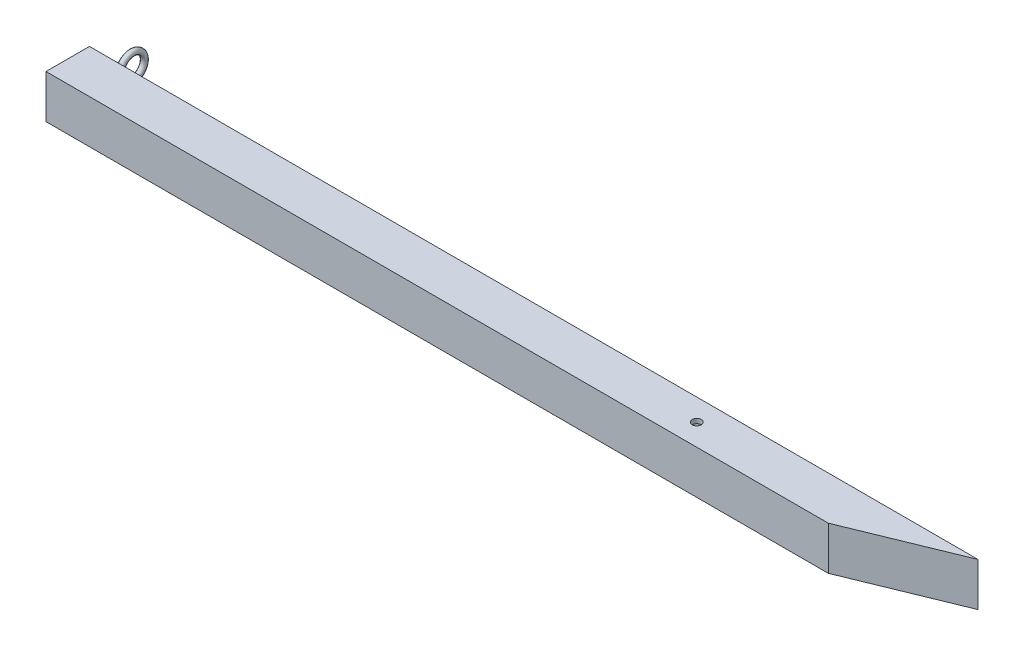
SolidWorks part; units mm, degrees
ref_plane "Front Plane" through (0, 0, 0) normal (0, 0, 1) x (1, 0, 0)
ref_plane "Top Plane" through (0, 0, 0) normal (0, 1, 0) x (1, 0, 0)
ref_plane "Right Plane" through (0, 0, 0) normal (1, 0, 0) x (0, 0, -1)
sketch "Sketch1" plane through (0, 0, 0) normal (0, 1, 0) x (1, 0, 0)
  line L0 (0, 0) -> (-762.6368, 0)
  dimension "D1" = 762.6368
sketch "Sketch2" plane through (0, 0, 0) normal (1, 0, 0) x (0, 0, -1)
  line L1 (19, 19) -> (-19, 19)
  line L2 (19, 19) -> (19, -19)
  line L3 (19, -19) -> (-19, -19)
  line L4 (-19, 19) -> (-19, -19)
  line L5 (19, 19) -> (-19, -19) construction
  line L6 (19, -19) -> (-19, 19) construction
  point P1 (0, 0)
  dimension "D1" = 38
  dimension "D2" = 38
sweep "Sweep1" add profiles "Sketch2" path "Sketch1"
sketch "Sketch3" plane through (0, 0, 0) normal (1, 0, 0) x (0, 0, -1)
  line L0 (-19, 19) -> (-19, -19) construction
  line L1 (15, 15) -> (-15, 15)
  line L2 (15, 15) -> (15, -15)
  line L3 (15, -15) -> (-15, -15)
  line L4 (-15, 15) -> (-15, -15)
  line L5 (15, 15) -> (-15, -15) construction
  line L6 (15, -15) -> (-15, 15) construction
  point P0 (0, 0)
  dimension "D1" = 4
sweep "Cut-Sweep1" cut profiles "Sketch3" path "Sketch1<2>"
sketch "Sketch1<2>" plane through (0, 0, 0) normal (0, 1, 0) x (1, 0, 0) same geometry as "Sketch1"
sketch "Sketch4" plane through (0, 19, 0) normal (0, 1, 0) x (1, 0, 0)
  line L0 (0, 0) -> (-212.6368, 0) construction
  circle A0 centre (-212.6368, 0) radius 4
  dimension "D2" = 8
  dimension "D1" = 212.6368
extrude "Cut-Extrude1" cut sketch "Sketch4" against normal through all
ref_plane "Plane1" through (-747.6368, 0, 0) normal (-1, 0, 0) x (0, 0, 1)
sketch "Sketch5" plane through (-747.6368, 0, 0) normal (-1, 0, 0) x (0, 0, 1)
  line L0 (-19, 0) -> (-26.5709, 0)
  line L1 (-19, -19) -> (-19, 19) construction
  arc A0 (-31.3213, 3.4397) -> (-31.3213, -3.1687) centre (-41.3809, 0.1355) ccw
  arc A1 (-26.5709, 0) -> (-31.3213, 3.4397) centre (-26.5709, 5) cw
  dimension "D1" = 5
sweep "Sweep2" add path "Sketch5" circular profile diameter 5 parameters "D3"=5
sketch "Sketch16" plane through (0, 19, 0) normal (0, 1, 0) x (1, 0, 0)
  line L0 (0, 19) -> (-71.9074, -19)
  line L1 (0, -19) -> (-762.6368, -19) construction
  line L2 (0, 19) -> (0, -19) construction
  line L3 (0, -19) -> (-762.6368, -19)
  line L4 (0, 19) -> (0, -19)
  line M4 (-762.6368, -19) -> (0, -19)
  line M5 (0, -19) -> (0, 19)
  dimension "D1" = 62.145
extrude "Cut-Extrude2" cut sketch "Sketch16" against normal through all contours L0 M5 M4 region at (-23.9691, 19, 6.3333)
sketch "Sketch17" plane through (0, 19, 0) normal (0, 1, 0) x (1, 0, 0)
  line L0 (-71.9074, -19) -> (0, -19)
  line L2 (0, -19) -> (71.9212, 19)
  line L3 (71.9212, 19) -> (71.9212, 7.6871) construction
  line L5 (0, 19) -> (71.9212, 19)
  line L6 (-71.9074, -19) -> (0, 19)
  dimension "D2" = 62.15
extrude "Boss-Extrude1" add sketch "Sketch17" against normal blind 38
sketch "Sketch22" plane through (-762.6368, 0, 0) normal (-1, 0, 0) x (0, 0, 1)
  line L0 (15, 15) -> (-15, 15) construction
  line L1 (15, 15) -> (-15, 15)
  line L2 (-15, -15) -> (15, -15) construction
  line L3 (-15, -15) -> (15, -15)
  line L4 (19, -19) -> (19, 19)
  line L5 (19, 19) -> (-19, 19)
  line L6 (-19, 19) -> (-19, -19)
  line L7 (-19, -19) -> (19, -19)
  line L8 (19, -19) -> (19, 19)
  line L9 (19, 19) -> (-19, 19)
  line L10 (-19, 19) -> (-19, -19)
  line L11 (-19, -19) -> (19, -19)
  line L12 (15, -15) -> (15, 15) construction
  line L13 (-15, 15) -> (-15, -15) construction
  line L14 (15, -15) -> (15, 15)
  line L15 (-15, 15) -> (-15, -15)
  dimension "D1" = 0
extrude "Cut-Extrude3" cut sketch "Sketch22" against normal through all contours L14 L1 L15 L3
sketch "Sketch23" plane through (0, 19, 0) normal (0, 1, 0) x (1, 0, 0)
  line L0 (-32.2068, -19) -> (0, -19)
  line L1 (-32.2068, 0) -> (14.2585, 0)
  line L2 (-32.2068, -19) -> (60.7238, 19)
  line L3 (0, -19) -> (-762.6368, -19) construction
  line L4 (-32.2068, -19) -> (-32.2068, 0)
  line L5 (71.9212, 19) -> (-762.6368, 19) construction
  line L7 (0, -19) -> (71.9212, 19)
  line L8 (71.9212, 19) -> (60.7238, 19)
  line L10 (-32.2068, 0) -> (-32.2068, 19)
  line L11 (-32.2068, 19) -> (60.7238, 19)
  line M5 (-762.6368, -19) -> (0, -19)
  line M6 (0, -19) -> (71.9212, 19)
  line M7 (71.9212, 19) -> (-762.6368, 19)
  dimension "D2" = 22.24
extrude "Cut-Extrude4" cut sketch "Sketch23" against normal through all contours L2 M5 M6 M7 region at (18.46, 19, 3.0656)
sketch "Sketch24" plane through (0, 19, 0) normal (0, 1, 0) x (1, 0, 0)
  line L2 (-78.6722, -19) -> (14.2585, 19)
  line L3 (-32.2068, -19) -> (-762.6368, -19) construction
  line L4 (60.7238, 19) -> (-762.6368, 19) construction
  line L5 (-32.2068, -19) -> (60.7238, 19) construction
  line L6 (60.7238, 19) -> (14.2585, 19)
  line L7 (-32.2068, -19) -> (60.7238, 19)
  line L8 (-32.2068, -19) -> (-78.6722, -19)
extrude "Cut-Extrude5" cut sketch "Sketch24" against normal through all
sketch "Sketch25" plane through (0, 19, 0) normal (0, 1, 0) x (1, 0, 0)
  line L0 (3.6901, 19) -> (-89.2406, -19)
  line L1 (14.2585, 19) -> (-762.6368, 19) construction
  line L2 (-78.6722, -19) -> (-762.6368, -19) construction
  line L3 (14.2585, 19) -> (-78.6722, -19) construction
  line L4 (3.6901, 19) -> (14.2585, 19)
  line L5 (14.2585, 19) -> (-78.6722, -19)
  line L6 (-78.6722, -19) -> (-89.2406, -19)
  dimension "D1" = 4
extrude "Boss-Extrude2" add sketch "Sketch25" against normal through all
